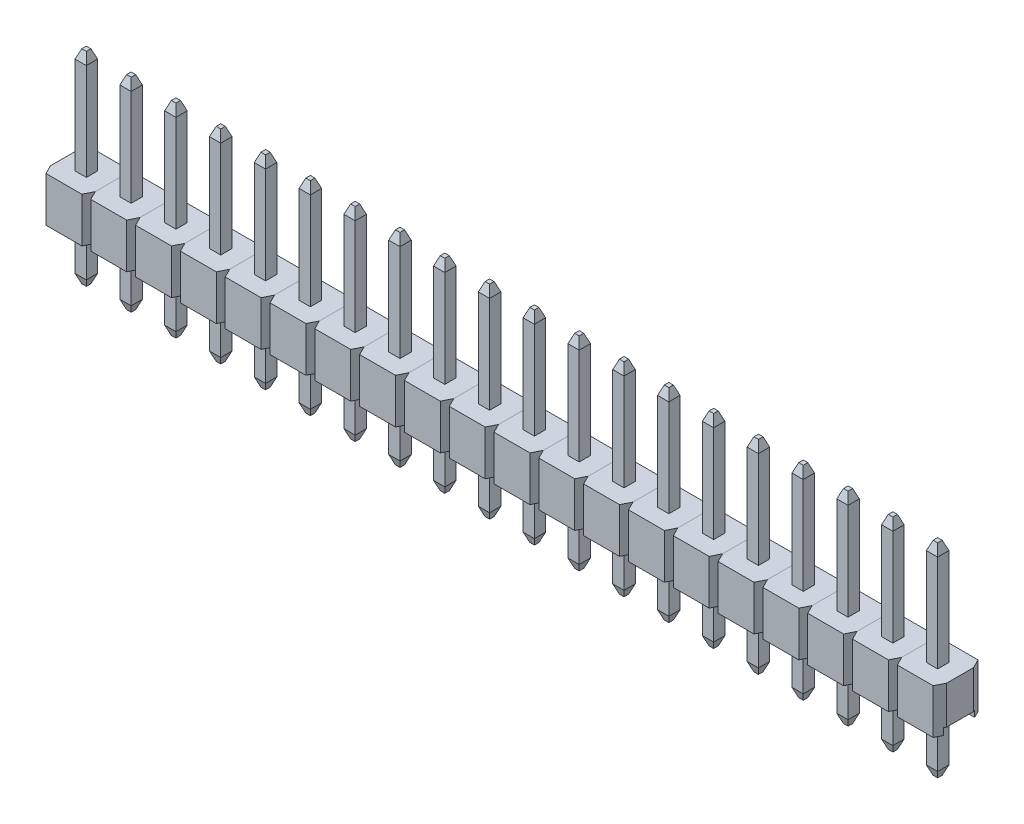
SolidWorks part; units mm, degrees
note: '?' marks a value the reader was unsure of.
ref_plane "Front Plane" through (0, 0, 0) normal (0, 0, 1) x (1, 0, 0)
ref_plane "Top Plane" through (0, 0, 0) normal (0, 1, 0) x (1, 0, 0)
ref_plane "Right Plane" through (0, 0, 0) normal (1, 0, 0) x (0, 0, -1)
sketch "Sketch1" plane through (0, 0, 0) normal (0, 1, 0) x (1, 0, 0)
  line L1 (0, 0) -> (2.54, 0)
  line L2 (0, 0) -> (0, 2.54)
  line L3 (0, 2.54) -> (2.54, 2.54)
  line L4 (2.54, 0) -> (2.54, 2.54)
  dimension "D1" = 2.54
  dimension "D2" = 2.54
extrude "plastic_housing" add sketch "Sketch1" along normal blind 2.54
sketch "Sketch3" plane through (0, 0, 0) normal (-1, 0, 0) x (0, 0, 1)
  line L0 (-2.54, 0) -> (0, 0) construction
  line L1 (-2.159, 0) -> (-0.381, 0)
  line L2 (-2.159, 0) -> (-2.159, 0.381)
  line L3 (-2.159, 0.381) -> (-0.381, 0.381)
  line L4 (-0.381, 0) -> (-0.381, 0.381)
  line L5 (-2.54, 0) -> (-2.159, 0) construction
  line L6 (-0.381, 0) -> (0, 0) construction
  dimension "D1" = 0.381
extrude "cut groove" cut sketch "Sketch3" against normal through all
sketch "SKETCH TOP POINT" plane through (0, 2.54, 0) normal (0, 1, 0) x (1, 0, 0)
  line L0 (0, 0) -> (2.54, 2.54) construction
  point P4 (1.27, 1.27)
sketch "SKETCH BOTTOM POINT" plane through (0, 0, 0) normal (0, -1, 0) x (1, 0, 0)
  point P0 (1.27, -1.27)
ref_axis "Axis1" through (1.27, 2.54, -1.27) along (0, -1, 0)?
sketch "Sketch4" plane through (0, 2.54, 0) normal (0, 1, 0) x (1, 0, 0)
  line L0 (0, 2.54) -> (0, 2.032)
  line L1 (0, 2.54) -> (0, 0) construction
  line L2 (0, 2.032) -> (0.254, 2.54)
  line L3 (2.54, 2.54) -> (0, 2.54) construction
  line L4 (0.254, 2.54) -> (0, 2.54)
  line L5 (2.54, 2.54) -> (2.286, 2.54)
  line L6 (2.286, 2.54) -> (2.54, 2.032)
  line L7 (2.54, 0) -> (2.54, 2.54) construction
  line L8 (2.54, 2.032) -> (2.54, 2.54)
  line L9 (2.54, 0) -> (2.286, 0)
  line L10 (0, 0) -> (2.54, 0) construction
  line L11 (2.286, 0) -> (2.54, 0.508)
  line L12 (2.54, 0.508) -> (2.54, 0)
  line L14 (0, 0) -> (0, 0.508)
  line L15 (0, 0.508) -> (0.254, 0)
  line L16 (0.254, 0) -> (0, 0)
  dimension "D1" = 0.254
  dimension "D2" = 0.508
extrude "cut corners" cut sketch "Sketch4" against normal through all
sketch "Sketch2" plane through (0, 2.54, 0) normal (0, 1, 0) x (1, 0, 0)
  line L0 (1.27, 2.54) -> (1.27, 1.59) construction
  line L1 (0.95, 0.95) -> (1.59, 0.95)
  line L2 (0.95, 0.95) -> (0.95, 1.59)
  line L3 (0.95, 1.59) -> (1.59, 1.59)
  line L4 (1.59, 0.95) -> (1.59, 1.59)
  line L6 (2.286, 2.54) -> (0.254, 2.54) construction
  line L8 (1.27, 0.95) -> (1.27, 0) construction
  line L9 (0.254, 0) -> (2.286, 0) construction
  dimension "D1" = 0.64
extrude "Pin" add sketch "Sketch2" along normal blind 6 and the other way offset from surface (5.54 mm away) 3 separate body other way up to face at (1.27, 0, -0.1905)
chamfer "chamf_bottom" distance 0.1905 distance2 0.508 4 edges at (1.27, -3, -1.59) (1.59, -3, -1.27) (1.27, -3, -0.95) (0.95, -3, -1.27)
chamfer "chamf_top" distance 0.508 distance2 0.1905 4 edges at (0.95, 8.54, -1.27) (1.27, 8.54, -1.59) (1.59, 8.54, -1.27) (1.27, 8.54, -0.95)
pattern_linear "pattern SLEEVE" count 20 spacing 2.54 along (-1, 0, 0) of "plastic_housing", "cut groove", "cut corners"
pattern_linear "pattern PINS" count 20 spacing 2.54 along (-1, 0, 0) of "Pin"
equation "\"pins\"= 20"
equation "\"D1@pattern SLEEVE\"=\"pins\""
equation "\"D1@pattern PINS\"=\"pins\""
